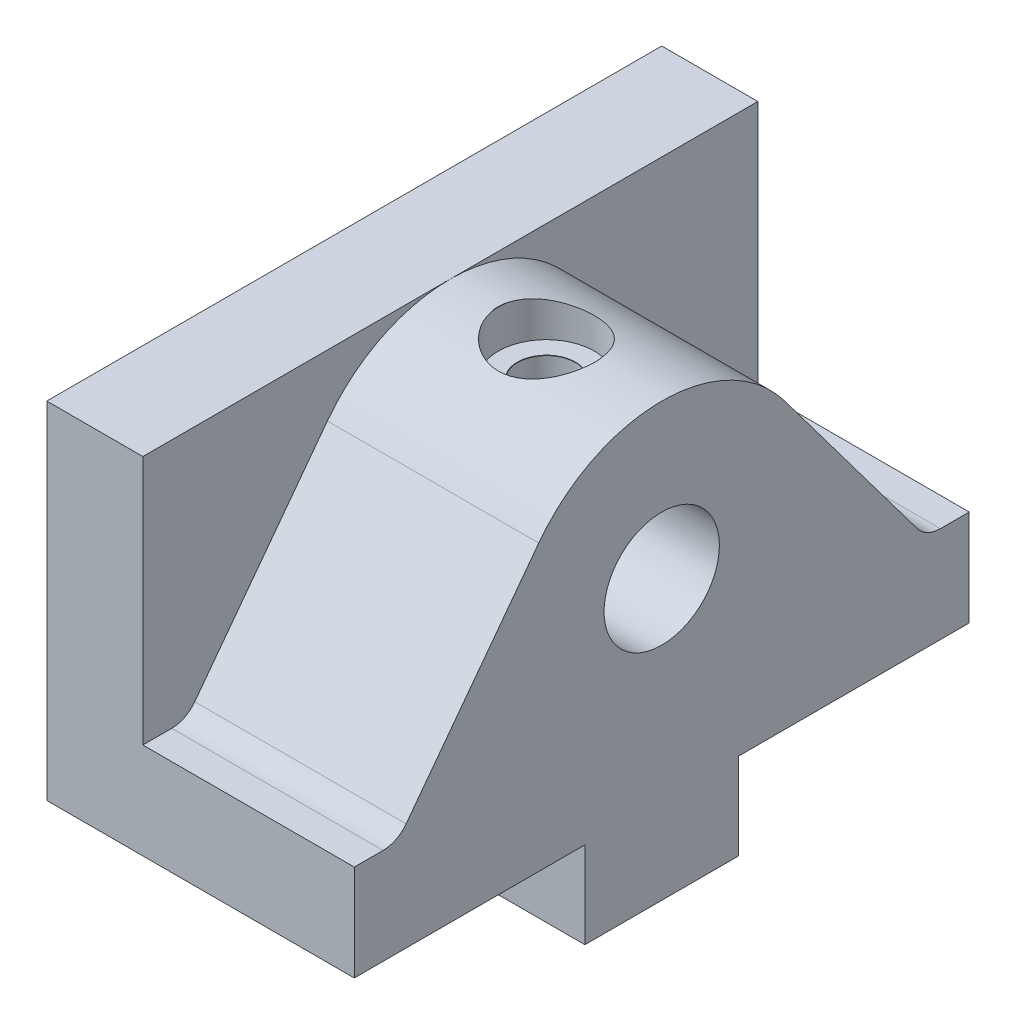
SolidWorks part; units mm, degrees
ref_plane "Front Plane" through (0, 0, 0) normal (0, 0, 1) x (1, 0, 0)
ref_plane "Top Plane" through (0, 0, 0) normal (0, 1, 0) x (1, 0, 0)
ref_plane "Right Plane" through (0, 0, 0) normal (1, 0, 0) x (0, 0, -1)
sketch "Sketch1" plane through (0, 0, 0) normal (1, 0, 0) x (0, 0, -1)
  line L0 (-8, 0) -> (8, 0)
  line L1 (-8, 0) -> (-8, 9)
  line L2 (8, 0) -> (8, 9)
  line L3 (-8, 9) -> (-32, 9)
  line L4 (8, 9) -> (32, 9)
  line L5 (-32, 9) -> (-32, 45)
  line L6 (32, 9) -> (32, 45)
  line L7 (-32, 45) -> (32, 45)
  point P4 (0, 0)
extrude "Boss-Extrude1" add sketch "Sketch1" along normal blind 10
sketch "Sketch2" plane through (10, 0, 0) normal (1, 0, 0) x (0, 0, -1)
  line L1 (-32, 9) -> (-32, 19)
  line L2 (-32, 45) -> (-32, 9) construction
  line L3 (-32, 19) -> (-27.5, 19)
  line L4 (-27.5, 19) -> (-12.8, 38.6)
  line L6 (27.5, 19) -> (12.8, 38.6)
  line L7 (32, 19) -> (27.5, 19)
  line L8 (32, 9) -> (32, 19)
  line L9 (8, 9) -> (32, 9)
  line L10 (8, 9) -> (8, 0)
  line L11 (8, 0) -> (-8, 0)
  line L12 (-8, 0) -> (-8, 9)
  line L13 (-8, 9) -> (-32, 9)
  arc A0 (12.8, 38.6) -> (-12.8, 38.6) centre (0, 29) ccw
extrude "Boss-Extrude2" add sketch "Sketch2" along normal blind 22
sketch "Sketch3" plane through (32, 0, 0) normal (1, 0, 0) x (0, 0, -1)
  line L0 (0, 0) -> (0, 45) construction
  line L1 (0, 45) -> (-32, 45) construction
  arc A0 (12.8, 38.6) -> (-12.8, 38.6) centre (0, 29) ccw construction
  circle A2 centre (0, 29) radius 6
  dimension "D1" = 16
extrude "Cut-Extrude1" cut sketch "Sketch3" against normal blind 24
sketch "Sketch4" plane through (0, 45, 0) normal (0, 1, 0) x (1, 0, 0)
  point P6 (20, 0)
hole_wizard "CBORE for M5 Hex Head Bolt1" positions "3DSketch1" profile "Sketch5" counterbore size "M5" standard "ISO" end condition up to next
sketch3d "3DSketch1"
  point P0 (20, 45, 0)
sketch "Sketch5" plane through (20, 45, 0) normal (1, 0, 0) x (0, 0, 1)
  line L0 (0, 0) -> (0, 10)
  line L1 (0, 10) -> (3, 10)
  line L3 (3, 4.025) -> (3.025, 4)
  line L4 (3.025, 4) -> (5, 4)
  line L5 (5, 4) -> (5, 0.025)
  line L6 (5, 0.025) -> (5.025, 0)
  line L7 (5.025, 0) -> (0, 0)
  line L8 (-5, 0.025) -> (-5.025, 0) construction
  line L9 (-3, 4.025) -> (-3.025, 4) construction
  line L10 (3, 10) -> (3, 4.025)
  line L11 (0, -6.35) -> (0, 107.95) construction
  dimension "Thru Hole Dia." = 6
  dimension "Thru Hole Depth" = 10
  dimension "C'Bore Dia." = 10
  dimension "C'Bore Depth" = 4
  dimension "Near C'Sink Dia." = 10.05
  dimension "Near C'Sink Angle" = 90
  dimension "Mid C'Sink Dia." = 6.05
  dimension "Mid C'Sink Angle" = 90
sketch "Sketch6" plane through (0, 9, 0) normal (0, -1, 0) x (1, 0, 0)
  point P5 (24, 0)
sketch "Sketch7" plane through (0, 9, 0) normal (0, -1, 0) x (1, 0, 0)
hole_wizard "Ø1.0mm Dowel Hole1" positions "3DSketch3" profile "Sketch9" hole size "Ø1.0" standard "ISO"
sketch3d "3DSketch3"
  line L0 (32, 0, 8) -> (32, 0, -8) construction
  point P0 (24, 0, 0)
  dimension "D1" = 8
sketch "Sketch9" plane through (24, 0, 0) normal (1, 0, 0) x (0, 0, -1)
  line L0 (0, 0) -> (0, 17.7321)
  line L1 (0, 17.7321) -> (3, 16)
  line L2 (3, 16) -> (3, 2.025)
  line L3 (3, 2.025) -> (5.025, 0)
  line L5 (5.025, 0) -> (0, 0)
  line L6 (-3, 2.025) -> (-5.025, 0) construction
  line L10 (0, 17.7321) -> (-3, 16) construction
  line L11 (0, -6.35) -> (0, 107.95) construction
  dimension "Hole Dia." = 6
  dimension "Hole Depth" = 16
  dimension "Near C'Sink Dia." = 10.05
  dimension "Near C'Sink Angle" = 90
  dimension "Drill Angle" = 120
pattern_linear "LPattern1" count 2 spacing 16 along (-1, 0, 0) of "Ø1.0mm Dowel Hole1"
fillet "Fillet1" radius 3 2 edges at (21, 19, 27.5) (21, 19, -27.5)
